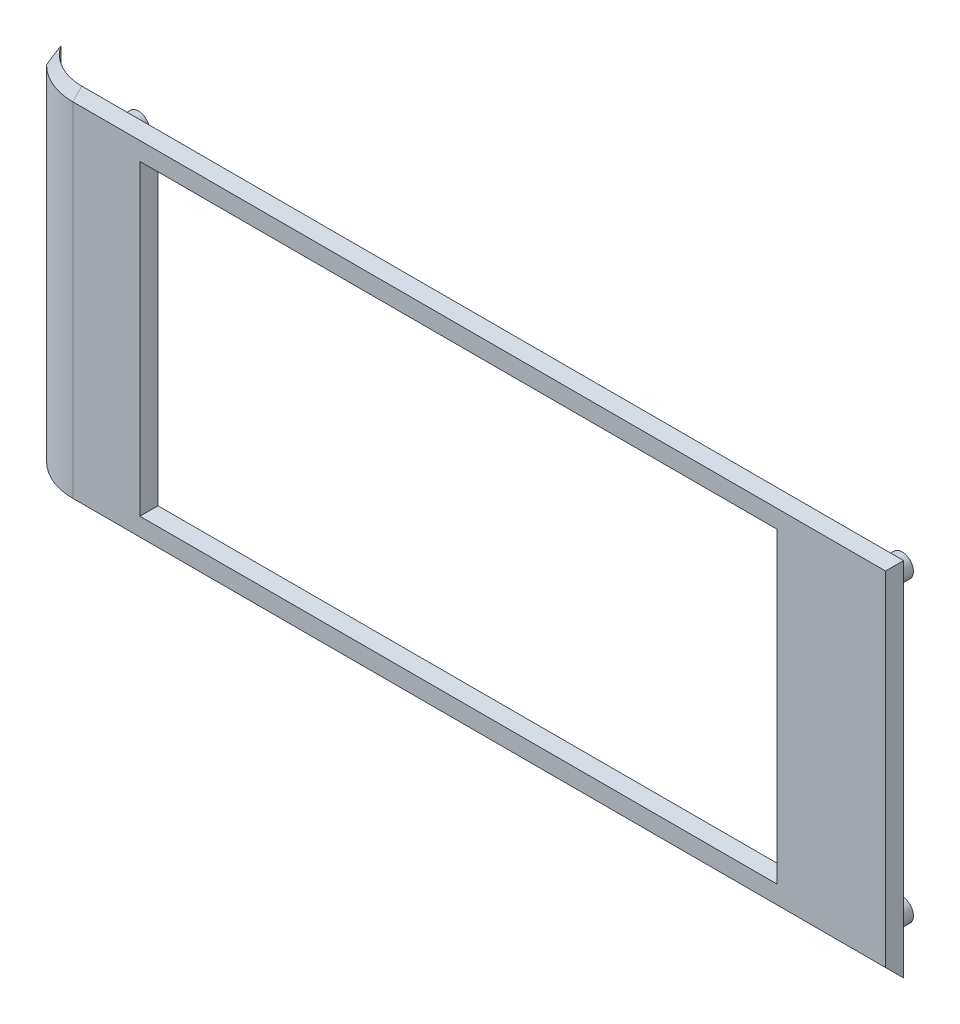
SolidWorks part; units mm, degrees
ref_plane "Front Plane" through (0, 0, 0) normal (0, 0, 1) x (1, 0, 0)
ref_plane "Top Plane" through (0, 0, 0) normal (0, 1, 0) x (1, 0, 0)
ref_plane "Right Plane" through (0, 0, 0) normal (1, 0, 0) x (0, 0, -1)
sketch "Sketch1" plane through (101441.594, 0, 0) normal (0, 0, 1) x (-1, 0, 0)
  line L1 (101382.019, 35) -> (101450.519, 35)
  line L2 (101382.019, 35) -> (101382.019, 3)
  line L3 (101382.019, 3) -> (101450.519, 3)
  line L8 (101458.949, 39) -> (101368.019, 39)
  line L9 (101458.949, -1) -> (101458.949, 39)
  line L10 (101368.019, -1) -> (101458.949, -1)
  line L11 (101368.019, 39) -> (101368.019, -1)
  line L12 (101450.519, 35) -> (101450.519, 3)
  point P8 (0, 0)
  point P9 (0, 0)
  point P10 (0, 0)
  point P15 (101370.1205, 49.9432)
  point P16 (101369.449, -21.0305)
  dimension "D2" = 68.5
  dimension "D3" = 14
  dimension "D4" = 4
  dimension "D5" = 4
  dimension "D6" = 90.93
  dimension "D1" = 40
extrude "Boss-Extrude1" add sketch "Sketch1" along normal blind 1
sketch "Sketch2" plane through (0, 0, 0) normal (0, 0, -1) x (-1, 0, 0)
  line L0 (-73.5751, 1) -> (17.3549, 1) construction
  line L1 (17.3549, -39) -> (-73.5751, -39) construction
  line L2 (-73.5751, -39) -> (-73.5751, 1) construction
  circle A0 centre (-70.4151, -2.5) radius 1.25
  circle A1 centre (-70.4151, -35.5) radius 1.25
  circle A2 centre (14.0849, -2.5) radius 1.25
  circle A3 centre (14.0849, -35.5) radius 1.25
  dimension "D4" = 2.5
  dimension "D1" = 3.5
  dimension "D2" = 3.5
  dimension "D3" = 3.16
  dimension "D5" = 2
extrude "Boss-Extrude2" add sketch "Sketch2" along normal blind 3
sketch "Sketch3" plane through (0, 1, 0) normal (0, 1, 0) x (1, 0, 0)
  line L0 (73.5751, 0) -> (-17.3549, 0) construction
  line L1 (-17.3549, -1) -> (-17.3549, 0) construction
  line L2 (-22.3549, 2.6834) -> (-22.3549, 1.101)
  line L3 (-17.3549, -1) -> (-17.3549, 0)
  arc A0 (-17.3549, 0) -> (-22.3549, 2.6834) centre (-17.3549, 6) cw
  arc A1 (-17.3549, -1) -> (-22.3549, 1.101) centre (-17.3549, 6) cw
  arc A3 (-17.3549, -1) -> (-23.1883, 2.1306) centre (-17.3549, 6) cw construction
  point P9 (-9.0835, 0.6617)
  dimension "D1" = 6
  dimension "D2" = 5
extrude "Boss-Extrude3" add sketch "Sketch3" against normal through all separate body
chamfer "Chamfer1" distance 1 angle 45 2 edges at (-20.0667, 1, 0.4534) (-20.0667, -39, 0.4534)
chamfer "Chamfer2" distance 1 angle 45 7 edges at (25.3251, -3, 1) (-8.9249, -19, 1) (25.3251, -35, 1) (59.5751, -19, 1) (28.1101, -39, 1) (73.5751, -19, 1) (28.1101, 1, 1)
